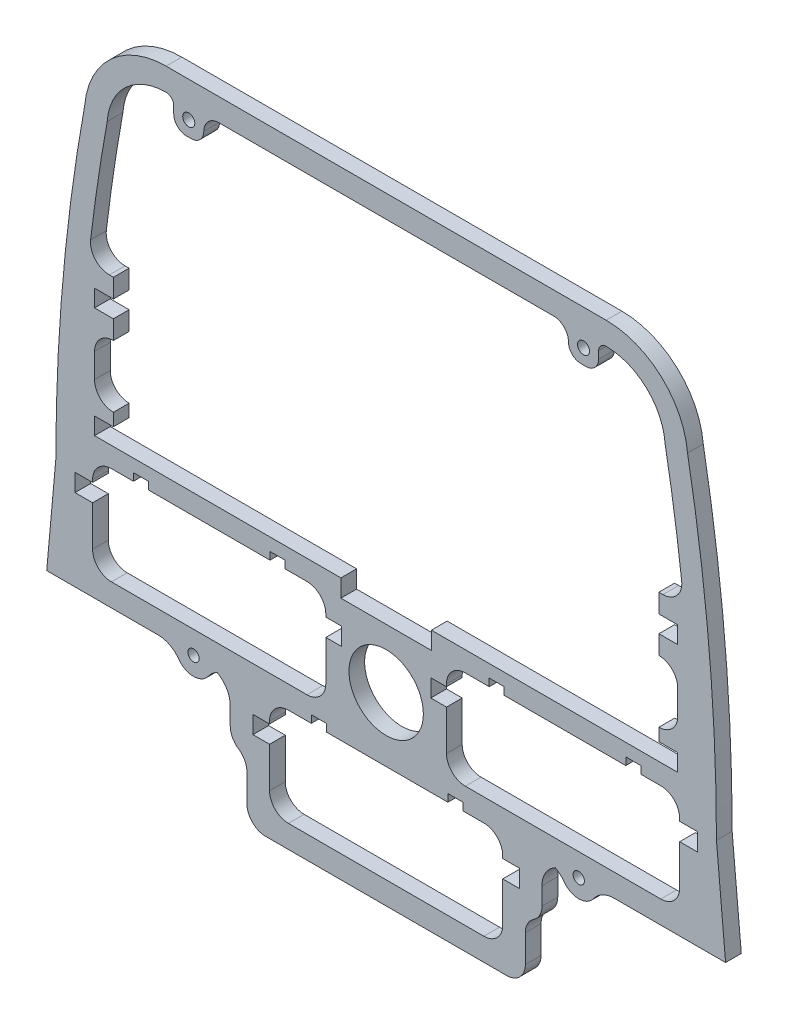
SolidWorks part; units mm, degrees
material "Delrin 2700 NC010, Low Viscosity Acetal Copolymer (SS)"
ref_plane "Front Plane" through (0, 0, 0) normal (0, 0, 1) x (1, 0, 0)
ref_plane "Top Plane" through (0, 0, 0) normal (0, 1, 0) x (1, 0, 0)
ref_plane "Right Plane" through (0, 0, 0) normal (1, 0, 0) x (0, 0, -1)
sketch "Sketch1" plane through (0, 0, 0) normal (0, 0, 1) x (1, 0, 0)
  line L0 (33.3676, -11.9888) -> (34.29, -22.225)
  line L1 (22.225, 27.94) -> (-22.225, 27.94)
  line L2 (-34.29, -22.225) -> (-30.4467, 20.4259) construction
  line L3 (-33.3676, -11.9888) -> (-33.3676, 14.6458) construction
  line L4 (-33.3676, -11.9888) -> (-34.29, -22.225)
  line L5 (16.9079, 25.654) -> (-16.9079, 25.654)
  line L6 (6.096, -13.97) -> (6.096, -19.939)
  line L7 (-29.6529, -19.939) -> (-6.096, -19.939)
  line L8 (-34.29, -22.225) -> (-21.299, -22.225)
  line L9 (-29.6529, -10.033) -> (-29.6529, -12.192)
  line L10 (18.4213, 24.1407) -> (18.4213, 24.1363)
  line L11 (19.6913, 22.8663) -> (20.1867, 22.8663)
  line L12 (21.4567, 24.1363) -> (21.4567, 24.8713)
  line L13 (-21.4567, 24.1363) -> (-21.4567, 24.8713)
  line L14 (-19.6913, 22.8663) -> (-20.1867, 22.8663)
  line L15 (-18.4213, 24.1407) -> (-18.4213, 24.1363)
  line L16 (29.4572, -8.001) -> (4.572, -8.001)
  line L17 (29.6529, -10.033) -> (25.7309, -10.033)
  line L18 (0, 18.415) -> (0, -18.415) construction
  line L19 (-1007.9925, 0) -> (48992.0075, 0) construction
  line L20 (-6.096, -10.033) -> (-10.2069, -10.033)
  line L21 (19.939, 24.384) -> (21.4567, 24.384) construction
  line L22 (6.096, -19.939) -> (29.6529, -19.939)
  line L23 (-6.096, -10.033) -> (-6.096, -12.192)
  line L24 (5.9491, -2.2098) -> (59.5431, -2.2098) construction
  line L25 (5.9491, -2.2098) -> (5.9491, -11.9888) construction
  line L26 (3.4091, -11.9888) -> (-3.4091, -11.9888) construction
  line L27 (59.5431, -2.2098) -> (59.5431, -11.9888) construction
  line L28 (-31.7887, -19.939) -> (31.7887, -19.939) construction
  line L29 (22.225, 25.654) -> (-22.225, 25.654) construction
  line L30 (-6.096, -19.939) -> (-6.1666, -19.9899)
  line L31 (29.4572, -6.2738) -> (27.5522, -6.2738)
  line L32 (27.5522, -6.2738) -> (27.5522, -5.0038)
  line L33 (-29.6529, -12.192) -> (-31.4309, -12.192)
  line L34 (27.5522, -5.0038) -> (29.4572, -5.0038)
  line L35 (29.4572, 1.27) -> (27.5522, 1.27)
  line L36 (27.5522, 1.27) -> (27.5522, 3.175)
  line L37 (27.5522, 3.175) -> (29.4572, 3.175)
  line L38 (29.4572, 4.9022) -> (27.5522, 4.9022)
  line L39 (19.939, 24.384) -> (18.4213, 24.384) construction
  line L40 (27.5522, 4.9022) -> (27.5522, 6.8072)
  line L41 (27.5522, 6.8072) -> (30.0922, 6.8072)
  line L42 (19.939, 24.384) -> (19.939, 22.8663) construction
  line L43 (6.096, -10.033) -> (6.096, -12.192)
  line L44 (-29.4572, -6.2738) -> (-29.4572, -8.001)
  line L45 (-29.4572, -6.2738) -> (-27.5522, -6.2738)
  line L46 (-27.5522, -6.2738) -> (-27.5522, -5.0038)
  line L47 (-27.5522, -5.0038) -> (-29.4572, -5.0038)
  line L48 (-29.4572, 1.27) -> (-29.4572, -5.0038)
  line L49 (-29.4572, 1.27) -> (-27.5522, 1.27)
  line L50 (-27.5522, 1.27) -> (-27.5522, 3.175)
  line L51 (-27.5522, 3.175) -> (-29.4572, 3.175)
  line L52 (-29.4572, 4.9022) -> (-29.4572, 3.175)
  line L53 (-31.4309, -12.192) -> (-31.4309, -13.97)
  line L54 (-31.4309, -13.97) -> (-29.6529, -13.97)
  line L55 (-6.096, -12.192) -> (-4.5069, -12.192)
  line L56 (-4.5069, -12.192) -> (-4.5069, -13.97)
  line L57 (-4.5069, -13.97) -> (-6.096, -13.97)
  line L58 (-29.6529, -10.033) -> (-29.6529, -19.939) construction
  line L59 (-29.6529, -14.986) -> (-33.4249, -14.986) construction
  line L60 (-29.6529, -14.986) -> (-0.4824, -14.986) construction
  line L61 (-6.096, -13.97) -> (-6.096, -19.939)
  line L62 (-29.6529, -19.939) -> (-29.6529, -13.97)
  line L63 (29.6529, -19.939) -> (29.6529, -13.97)
  line L64 (-31.0816, -12.0913) -> (-31.7887, -19.939) construction
  line L65 (29.6529, -10.033) -> (29.6529, -12.192)
  line L66 (31.4309, -13.97) -> (29.6529, -13.97)
  line L67 (31.4309, -12.192) -> (31.4309, -13.97)
  line L68 (29.6529, -12.192) -> (31.4309, -12.192)
  line L69 (6.096, -12.192) -> (4.5069, -12.192)
  line L70 (4.5069, -12.192) -> (4.5069, -13.97)
  line L71 (4.5069, -13.97) -> (6.096, -13.97)
  line L72 (29.4572, 4.9022) -> (29.4572, 3.175)
  line L73 (31.0816, -12.0913) -> (31.7887, -19.939) construction
  line L74 (29.4572, 1.27) -> (29.4572, -5.0038)
  line L75 (29.4572, -6.2738) -> (29.4572, -8.001)
  line L76 (-29.4572, 4.9022) -> (-27.5522, 4.9022)
  line L77 (-27.5522, 4.9022) -> (-27.5522, 6.8072)
  line L78 (-27.5522, 6.8072) -> (-30.0922, 6.8072)
  line L79 (-17.616, -22.225) -> (-15.7485, -22.225)
  line L80 (21.299, -22.225) -> (34.29, -22.225)
  line L81 (-34.29, -22.225) -> (34.29, -22.225) construction
  line L82 (-4.572, -8.001) -> (-4.572, -9.779)
  line L83 (-4.572, -9.779) -> (0, -9.779)
  line L84 (0, -9.779) -> (4.572, -9.779)
  line L85 (4.572, -9.779) -> (4.572, -8.001)
  line L86 (-4.572, -8.001) -> (-29.4572, -8.001)
  line L87 (-11.7784, -22.225) -> (-11.7784, -24.384)
  line L88 (-11.7784, -24.384) -> (-13.4625, -24.384)
  line L89 (-13.4625, -24.384) -> (-13.4625, -26.162)
  line L90 (-13.4625, -26.162) -> (-11.7784, -26.162)
  line L91 (-11.7784, -26.162) -> (-11.7784, -32.131)
  line L92 (-11.7784, -32.131) -> (11.7784, -32.131)
  line L93 (11.7784, -32.131) -> (11.7784, -26.162)
  line L94 (11.7784, -26.162) -> (13.4625, -26.162)
  line L95 (13.4625, -26.162) -> (13.4625, -24.384)
  line L96 (13.4625, -24.384) -> (11.7784, -24.384)
  line L97 (11.7784, -24.384) -> (11.7784, -22.225)
  line L98 (11.7784, -22.225) -> (-11.7784, -22.225) construction
  line L99 (0, -32.131) -> (0, -22.225) construction
  line L100 (-11.7784, -22.225) -> (-7.562, -22.225)
  line L101 (-15.7485, -22.098) -> (-15.7485, -28.448) construction
  line L102 (-15.7485, -22.225) -> (-15.7485, -28.448)
  line L103 (-15.7485, -28.448) -> (-14.0644, -28.448)
  line L104 (-14.0644, -28.448) -> (-14.0644, -34.417)
  line L105 (-14.0644, -34.417) -> (14.0644, -34.417)
  line L106 (14.0644, -34.417) -> (14.0644, -28.448)
  line L107 (14.0644, -28.448) -> (15.7485, -28.448)
  line L108 (15.7485, -28.448) -> (15.7485, -22.225)
  line L109 (15.7485, -22.225) -> (17.616, -22.225)
  line L110 (15.7485, -28.448) -> (15.7485, -22.098) construction
  line L111 (15.7485, -22.098) -> (14.0609, -22.098) construction
  line L112 (14.0609, -22.098) -> (14.0609, -22.098) construction
  line L113 (-14.0609, -22.098) -> (-14.0609, -22.098) construction
  line L114 (-14.0609, -22.098) -> (-15.7485, -22.098) construction
  line L115 (-11.7309, -10.033) -> (-24.0069, -10.033)
  line L116 (7.762, -22.2885) -> (6.238, -22.2885) construction
  line L117 (11.9309, -10.1918) -> (10.4069, -10.1918) construction
  line L118 (-24.0069, -10.1917) -> (-25.5309, -10.1917) construction
  line L119 (-25.5309, -10.033) -> (-29.6529, -10.033)
  line L120 (10.4069, -10.033) -> (6.096, -10.033)
  line L121 (-10.2069, -10.1917) -> (-11.7309, -10.1917) construction
  line L122 (25.7309, -10.1918) -> (24.2069, -10.1918) construction
  line L123 (24.2069, -10.033) -> (11.9309, -10.033)
  line L124 (7.762, -22.225) -> (11.7784, -22.225)
  line L125 (11.9309, -10.1918) -> (10.4069, -10.1918) construction
  line L126 (-24.0069, -10.1917) -> (-25.5309, -10.1917) construction
  line L127 (-6.038, -22.225) -> (6.238, -22.225)
  line L136 (-10.2069, -10.1917) -> (-11.7309, -10.1917) construction
  line L137 (25.7309, -10.1918) -> (24.2069, -10.1918) construction
  line L138 (-25.5309, -10.1917) -> (-25.5309, -9.271)
  line L139 (-25.5309, -9.271) -> (-24.0069, -9.271)
  line L140 (-24.0069, -9.271) -> (-24.0069, -10.1917)
  line L141 (-11.7309, -10.1917) -> (-11.7309, -9.271)
  line L142 (-11.7309, -9.271) -> (-10.2069, -9.271)
  line L143 (-10.2069, -9.271) -> (-10.2069, -10.1917)
  line L144 (10.4069, -10.1918) -> (10.4069, -9.271)
  line L145 (10.4069, -9.271) -> (11.9309, -9.271)
  line L146 (11.9309, -9.271) -> (11.9309, -10.1918)
  line L147 (24.2069, -10.1918) -> (24.2069, -9.271)
  line L152 (7.762, -22.2885) -> (6.238, -22.2885) construction
  line L153 (-6.038, -22.2885) -> (-7.562, -22.2885) construction
  line L154 (-6.038, -22.2885) -> (-7.562, -22.2885) construction
  line L155 (24.2069, -9.271) -> (25.7309, -9.271)
  line L156 (25.7309, -9.271) -> (25.7309, -10.1918)
  line L157 (-7.562, -22.2885) -> (-7.562, -21.463)
  line L158 (-7.562, -21.463) -> (-6.038, -21.463)
  line L159 (-6.038, -21.463) -> (-6.038, -22.2885)
  line L160 (6.238, -22.2885) -> (6.238, -21.463)
  line L161 (6.238, -21.463) -> (7.762, -21.463)
  line L162 (7.762, -21.463) -> (7.762, -22.2885)
  arc A0 (22.225, 27.94) -> (30.4467, 20.4259) centre (22.225, 19.685) cw
  arc A1 (-22.225, 27.94) -> (-30.4467, 20.4259) centre (-22.225, 19.685) ccw
  arc A2 (33.3676, -11.9888) -> (30.4467, 20.4259) centre (-147.9525, -11.9888) ccw
  circle A3 centre (0, -15.748) radius 3.7592
  circle A4 centre (19.4575, -22.225) radius 0.5715
  arc A5 (-33.3676, -11.9888) -> (-30.4467, 20.4259) centre (147.9525, -11.9888) cw
  arc A6 (-17.616, -22.225) -> (-21.299, -22.225) centre (-19.4575, -22.225) cw
  arc A7 (17.616, -22.225) -> (21.299, -22.225) centre (19.4575, -22.225) ccw
  arc A8 (20.1867, 22.8663) -> (21.4567, 24.1363) centre (20.1867, 24.1363) ccw
  circle A9 centre (-19.939, 24.384) radius 0.6096
  circle A10 centre (19.939, 24.384) radius 0.6096
  arc A11 (18.4213, 24.1363) -> (19.6913, 22.8663) centre (19.6913, 24.1363) ccw
  circle A12 centre (-19.4575, -22.225) radius 0.5715
  arc A13 (18.4213, 24.1407) -> (16.9079, 25.654) centre (16.9079, 24.1407) ccw
  arc A14 (22.2416, 25.654) -> (21.4567, 24.8713) centre (22.2394, 24.8713) ccw
  arc A15 (-22.2416, 25.654) -> (-21.4567, 24.8713) centre (-22.2394, 24.8713) cw
  arc A16 (-20.1867, 22.8663) -> (-21.4567, 24.1363) centre (-20.1867, 24.1363) cw
  arc A17 (-18.4213, 24.1363) -> (-19.6913, 22.8663) centre (-19.6913, 24.1363) cw
  arc A18 (-22.2416, 25.654) -> (-28.1777, 20.1262) centre (-22.225, 19.685) ccw
  arc A19 (-18.4213, 24.1407) -> (-16.9079, 25.654) centre (-16.9079, 24.1407) cw
  arc A20 (31.0816, -12.0913) -> (31.0816, -11.9888) centre (-147.9525, -11.9888) ccw
  circle A21 centre (-19.4575, -22.225) radius 1.8415 construction
  arc A23 (22.2416, 25.654) -> (28.1777, 20.1262) centre (22.225, 19.685) cw
  arc A25 (-22.225, 25.654) -> (-28.1777, 20.1262) centre (-22.225, 19.685) ccw construction
  arc A26 (22.225, 25.654) -> (28.1777, 20.1262) centre (22.225, 19.685) cw construction
  arc A28 (-31.0816, -12.0913) -> (-28.1777, 20.1262) centre (147.9525, -11.9888) cw construction
  arc A30 (31.0816, -12.0913) -> (28.1777, 20.1262) centre (-147.9525, -11.9888) ccw construction
  arc A31 (30.0922, 6.8072) -> (28.1777, 20.1262) centre (-147.9525, -11.9888) ccw
  arc A33 (-30.0922, 6.8072) -> (-28.1777, 20.1262) centre (147.9525, -11.9888) cw
  point P0 (0, 0)
  point P1 (0, 27.94)
  point P31 (0, -11.9888)
  point P121 (-30.9018, -14.986)
  point P135 (-17.616, -22.225)
  dimension "D4" = 2.286
  dimension "D6" = 8.255
  dimension "D7" = 19.4575
  dimension "D8" = 50.165
  dimension "D9" = 15.748
  dimension "D5" = 1.2192
  dimension "D17" = 1.143
  dimension "D3" = 7.5184
  dimension "D18" = 1.27
  dimension "D19" = 1.27
  dimension "D26" = 11.176
  dimension "D28" = 0.7827
  dimension "D29" = 1.5133
  dimension "D32" = 1.778
  dimension "D2" = 44.45
  dimension "D10" = 1.27
  dimension "D11" = 1.27
  dimension "D12" = 68.58
  dimension "D13" = 19.939
  dimension "D14" = 22.225
  dimension "D15" = 53.594
  dimension "D16" = 9.779
  dimension "D20" = 6.096
  dimension "D21" = 11.938
  dimension "D22" = 2.032
  dimension "D23" = 1.7272
  dimension "D24" = 1.27
  dimension "D25" = 1.905
  dimension "D27" = 0.4954
  dimension "D30" = 1.905
  dimension "D31" = 1.7272
  dimension "D33" = 1.778
  dimension "D34" = 2.159
  dimension "D35" = 23.5569
  dimension "D36" = 26.924
  dimension "D37" = 1.905
  dimension "D38" = 2.54
  dimension "D39" = 1.778
  dimension "D40" = 9.144
  dimension "D42" = 0.762
  dimension "D43" = 0.762
  dimension "D44" = 1.684
  dimension "D41" = 2.286
extrude "Boss-Extrude1" add sketch "Sketch1" along normal blind 1.5875 contours L8 A12 A4 L0 A2 A0 L1 A1 A5 L4 L74 L16 A18 A15 L13 A16 L14 A17 L15 A19 L5 A13 L10 A11 L11 A8 L12 A14 A23 A20 L22 L43 L17 A10 A9 A3 L20 region at (32.9056, -17.1901, 0)
ref_axis "Axis1" through (0, -15.748, 0) along (0, 0, 1)
fillet "Fillet1" radius 1.905 12 edges at (-6.096, -10.033, 0.7937) (-6.096, -19.939, 0.7937) (-29.6529, -19.939, 0.7937) (6.096, -19.939, 0.7937) (29.6529, -19.939, 0.7937) (29.6529, -10.033, 0.7937) (11.7784, -32.131, 0.7937) (-11.7784, -32.131, 0.7937) (-11.7784, -22.225, 0.7937) (11.7784, -22.225, 0.7937) (6.096, -10.033, 0.7937) (-29.6529, -10.033, 0.7937)
fillet "Fillet2" radius 1.905 6 edges at (-29.4572, 1.27, 0.7937) (-29.4572, -5.0038, 0.7937) (-30.0922, 6.8072, 0.7937) (29.4572, -5.0038, 0.7937) (29.4572, 1.27, 0.7937) (30.0922, 6.8072, 0.7937)
fillet "Fillet3" radius 2.54 6 edges at (-17.616, -22.225, 0.7937) (-21.299, -22.225, 0.7937) (21.299, -22.225, 0.7937) (17.616, -22.225, 0.7937) (15.7485, -22.225, 0.7937) (-15.7485, -22.225, 0.7937)
fillet "Fillet4" radius 1.905 4 edges at (15.7485, -28.448, 0.7937) (14.0644, -34.417, 0.7937) (-14.0644, -34.417, 0.7937) (-15.7485, -28.448, 0.7937)
fillet "Fillet5" radius 1.905 2 edges at (14.0644, -28.448, 0.7937) (-14.0644, -28.448, 0.7937)
